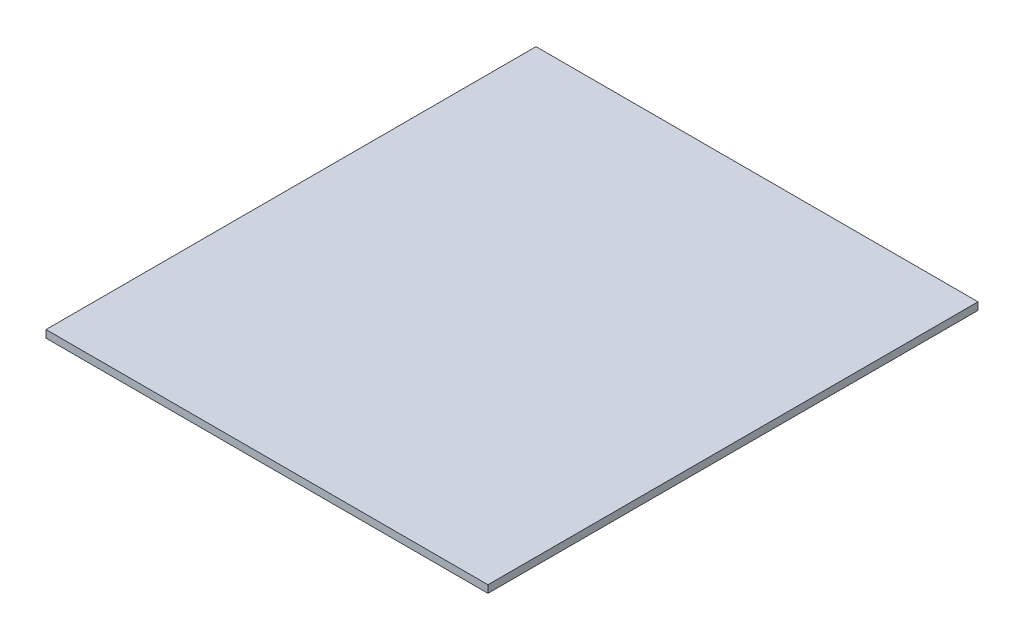
SolidWorks part; units mm, degrees
ref_plane "Front Plane" through (0, 0, 0) normal (0, 0, 1) x (1, 0, 0)
ref_plane "Top Plane" through (0, 0, 0) normal (0, 1, 0) x (1, 0, 0)
ref_plane "Right Plane" through (0, 0, 0) normal (1, 0, 0) x (0, 0, -1)
sketch "Sketch1" plane through (0, 0, 0) normal (0, 1, 0) x (1, 0, 0)
  line L1 (25, -27.5) -> (-25, -27.5)
  line L2 (25, -27.5) -> (25, 27.5)
  line L3 (25, 27.5) -> (-25, 27.5)
  line L4 (-25, -27.5) -> (-25, 27.5)
  line L5 (25, -27.5) -> (-25, 27.5) construction
  line L6 (25, 27.5) -> (-25, -27.5) construction
  line L7 (23, -25.5) -> (-23, -25.5)
  line L8 (23, -25.5) -> (23, 25.5)
  line L9 (23, 25.5) -> (-23, 25.5)
  line L10 (-23, -25.5) -> (-23, 25.5)
  line L11 (23, -25.5) -> (-23, 25.5) construction
  line L12 (23, 25.5) -> (-23, -25.5) construction
  point P0 (0, 0)
  point P6 (0, 0)
  dimension "D1" = 50
  dimension "D2" = 55
  dimension "D3" = 2
  dimension "D4" = 2
extrude "Boss-Extrude1" add sketch "Sketch1" along normal blind 0.78 contours L10 L7 L8 L9 region at (0, 0, 0)
